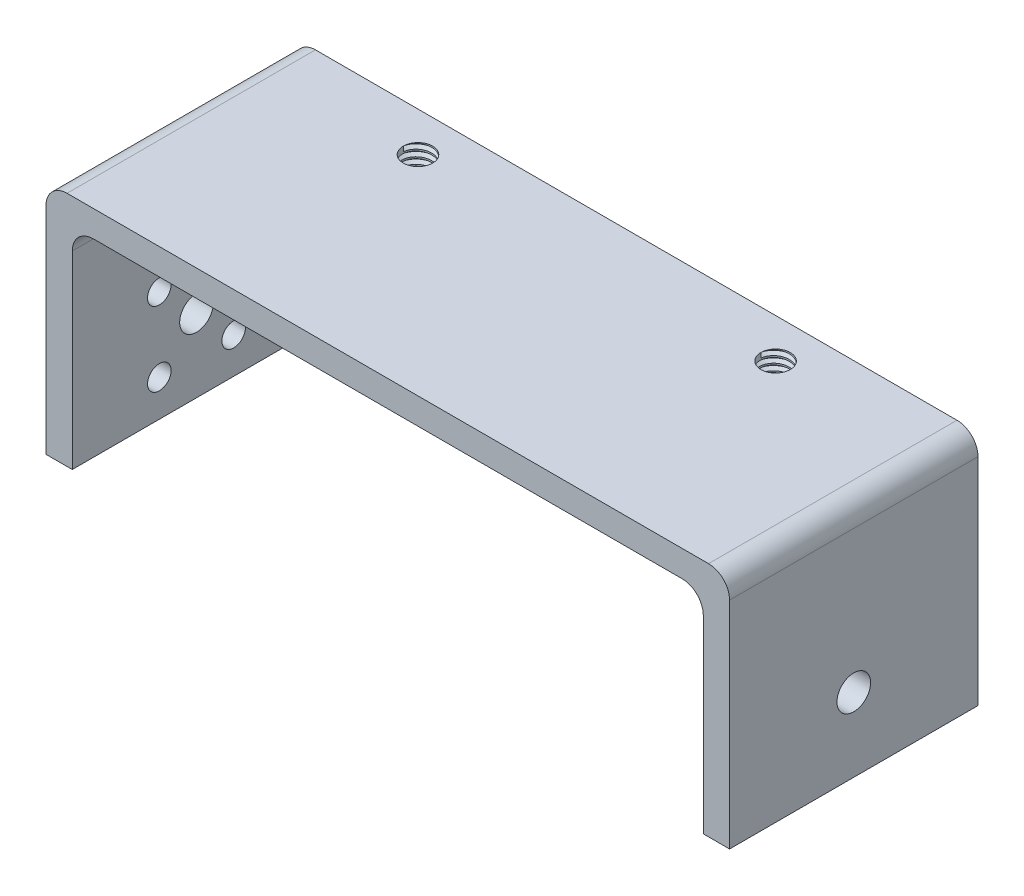
SolidWorks part; units mm, degrees
ref_plane "Front Plane" through (0, 0, 0) normal (0, 0, 1) x (1, 0, 0)
ref_plane "Top Plane" through (0, 0, 0) normal (0, 1, 0) x (1, 0, 0)
ref_plane "Right Plane" through (0, 0, 0) normal (1, 0, 0) x (0, 0, -1)
sketch "Sketch1" plane through (0, 0, 0) normal (0, 1, 0) x (1, 0, 0)
  line L1 (-41.275, -15) -> (41.275, -15)
  line L2 (-41.275, -15) -> (-41.275, 15)
  line L3 (-41.275, 15) -> (41.275, 15)
  line L4 (41.275, -15) -> (41.275, 15)
  line L5 (-41.275, -15) -> (41.275, 15) construction
  line L6 (-41.275, 15) -> (41.275, -15) construction
  point P0 (0, 0)
  dimension "D1" = 41.275
  dimension "D2" = 30
extrude "Boss-Extrude1" add sketch "Sketch1" along normal blind 3.175
sketch "Sketch2" plane through (0, 0, 0) normal (0, -1, 0) x (1, 0, 0)
  line L0 (-41.275, -15) -> (-41.275, 15) construction
  line L1 (-41.275, -15) -> (-38.1, -15)
  line L3 (-41.275, 15) -> (-38.1, 15)
  line L4 (-38.1, -15) -> (-38.1, 15)
  line L5 (-41.275, 15) -> (-41.275, -15)
  line L6 (0, -28.3834) -> (0, 28.3834) construction
  line L7 (-41.275, 15) -> (41.275, 15) construction
  line L8 (41.275, 15) -> (41.275, -15)
  line L9 (38.1, -15) -> (38.1, 15)
  line L10 (41.275, 15) -> (38.1, 15)
  line L11 (41.275, -15) -> (38.1, -15)
  point P0 (-41.275, 0)
  point P13 (0, 0)
  point P19 (41.275, 0)
  dimension "D1" = 3.175
extrude "Boss-Extrude2" add sketch "Sketch2" along normal blind 25.4
sketch "Sketch3" plane through (41.275, 0, 0) normal (1, 0, 0) x (0, 0, -1)
  line L0 (15, -25.4) -> (-15, -25.4) construction
  circle A0 centre (0, -16.51) radius 2.032
  point P4 (0, -25.4)
  dimension "D2" = 4.064
  dimension "D1" = 8.89
extrude "Cut-Extrude1" cut sketch "Sketch3" against normal through all
sketch "Sketch4" plane through (-41.275, 0, 0) normal (1, 0, 0) x (0, 0, -1)
  line L0 (0, -16.51) -> (8.7185, -16.51) construction
  line L1 (0, -16.51) -> (6.0933, -10.4167) construction
  circle A0 centre (0, -16.51) radius 6.35 construction
  circle A1 centre (4.4901, -12.0199) radius 1.4224
  circle A2 centre (4.4901, -21.0001) radius 1.4224
  circle A3 centre (-4.4901, -21.0001) radius 1.4224
  circle A4 centre (-4.4901, -12.0199) radius 1.4224
  point P16 (0, -16.51)
  dimension "D1" = 12.7
  dimension "D3" = 2.8448
  dimension "D2" = 45
  dimension "D4" = 4
extrude "Cut-Extrude2" cut sketch "Sketch4" along normal up to surface (3.175 mm away) up to face at (-38.1, -16.51, 2.032)
sketch "Sketch5" plane through (0, 3.175, 0) normal (0, 1, 0) x (1, 0, 0)
  line L0 (0, -19.5395) -> (0, 19.5395) construction
  line L5 (41.275, 15) -> (-41.275, 15) construction
  circle A4 centre (21.59, 10.2375) radius 1.778
  circle A5 centre (-21.59, 10.2375) radius 1.778
  point P0 (0, 0)
  point P10 (0, 0)
  point P13 (0, 0)
  dimension "D3" = 21.59
  dimension "D1" = 3.556
  dimension "D2" = 4.7625
extrude "Cut-Extrude3" cut sketch "Sketch5" against normal up to surface (3.175 mm away) up to face at (0, 0, 0)
fillet "Fillet1" radius 2.54 4 edges at (41.275, 3.175, 0) (-41.275, 3.175, 0) (38.1, 0, 0) (-38.1, 0, 0)
thread "Thread1" pitch 0.7937 method cut profile "Thread Profile1" start angle 0, offset 0, length 0, pitch 0.7937, diameter 3.556
ref_plane "Plane1" through (-23.368, 3.175, -10.2375) normal (0, 0, 1) x (-1, 0, 0)
sketch "Thread Profile1" plane through (-23.368, 3.175, -10.2375) normal (0, 0, 1) x (-1, 0, 0)
  line L0 (0, 0) -> (0, 0.7937) construction
  line L1 (0, 0) -> (0.4296, 0.248)
  line L2 (0.4296, 0.248) -> (0.4296, 0.3473)
  line L3 (0.4296, 0.3473) -> (0, 0.5953)
  line L4 (0.4296, 0.2977) -> (0, 0.2977) construction
  line L11 (0, 0) -> (0, 0.5953)
  point P2 (0, 0)
  dimension "Pitch" = 0.7937
  dimension "Profile_Angle" = 60
  dimension "Profile_Land" = 0.0992
  dimension "Profile_Height" = 0.4296
thread "Thread2" pitch 0.7937 method cut profile "Thread Profile2" start angle 0, offset 0, length 0, pitch 0.7937, diameter 3.556
ref_plane "Plane2" through (19.812, 3.175, -10.2375) normal (0, 0, 1) x (-1, 0, 0)
sketch "Thread Profile2" plane through (19.812, 3.175, -10.2375) normal (0, 0, 1) x (-1, 0, 0)
  line L0 (0, 0) -> (0, 0.7937) construction
  line L1 (0, 0) -> (0.4296, 0.248)
  line L2 (0.4296, 0.248) -> (0.4296, 0.3473)
  line L3 (0.4296, 0.3473) -> (0, 0.5953)
  line L4 (0.4296, 0.2977) -> (0, 0.2977) construction
  line L11 (0, 0) -> (0, 0.5953)
  point P2 (0, 0)
  dimension "Pitch" = 0.7937
  dimension "Profile_Angle" = 60
  dimension "Profile_Land" = 0.0992
  dimension "Profile_Height" = 0.4296
